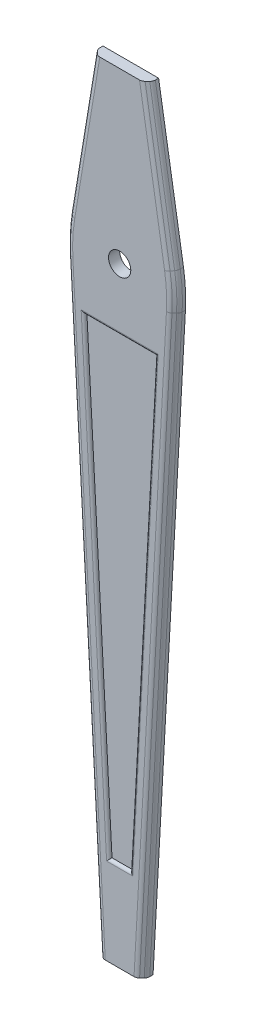
SolidWorks part; units mm, degrees
ref_plane "Front" through (0, 0, 0) normal (0, 0, 1) x (1, 0, 0)
ref_plane "Top" through (0, 0, 0) normal (0, 1, 0) x (1, 0, 0)
ref_plane "Right" through (0, 0, 0) normal (1, 0, 0) x (0, 0, -1)
sketch "Эскиз1" plane through (0, 0, 0) normal (0, 0, 1) x (1, 0, 0)
  line L0 (-1.8457, 0) -> (2.0484, 0) construction
  line L1 (0, 3.2545) -> (0, -2.3671) construction
  line L2 (-0.9468, 0.3235) -> (-0.5, 3.04)
  line L3 (-0.5, 3.04) -> (0.5, 3.04)
  line L4 (-0.9821, -0.3274) -> (-0.4, -10.96)
  line L5 (-0.4, -10.96) -> (0.4, -10.96)
  line L6 (0.9821, -0.3274) -> (0.4, -10.96)
  line L7 (0.9468, 0.3235) -> (0.5, 3.04)
  circle A0 centre (0, 0) radius 0.2
  arc A1 (0.9821, -0.3274) -> (0.9468, 0.3235) centre (-2.0134, -0.1634) ccw
  arc A2 (-0.9468, 0.3235) -> (-0.9821, -0.3274) centre (2.0134, -0.1634) ccw
  point P13 (0, -10.96)
  point P15 (0, 3.04)
  point P17 (1, 0)
  point P20 (-1, 0)
  dimension "D1" = 0.4
  dimension "D7" = 3
  dimension "D2" = 10.96
  dimension "D3" = 0.4
  dimension "D4" = 0.5
  dimension "D5" = 1
  dimension "D6" = 3.04
extrude "Бобышка-Вытянуть1" add sketch "Эскиз1" along normal blind 0.2
chamfer "Фаска1" distance 0.1 angle 45 6 edges at (0.691, -5.6437, 0.2) (0.7234, 1.6818, 0.2) (-0.7234, 1.6818, 0.2) (-0.691, -5.6437, 0.2) (0.9822, -0.001, 0.2) (-0.9822, -0.001, 0.2)
sketch "Эскиз2" plane through (0, 0, 0.2) normal (0, 0, 1) x (1, 0, 0)
  line L2 (-0.6825, -0.311) -> (-0.1001, -10.9491)
  line L3 (-0.6389, -1.1086) -> (-0.1872, -9.3583)
  line L5 (0.1001, -10.9491) -> (0.6825, -0.311)
  line L6 (0.1872, -9.3583) -> (0.6389, -1.1086)
  line L10 (-0.1872, -9.3583) -> (0.1872, -9.3583)
  line L11 (-0.2999, -10.96) -> (0.2999, -10.96) construction
  line L12 (-0.6389, -1.1086) -> (0.6389, -1.1086)
  dimension "D1" = 0.2
  dimension "D2" = 0.2
extrude "Вырез-Вытянуть1" cut sketch "Эскиз2" against normal blind 0.05
fillet "Скругление1" radius 0.1 12 edges at (0.7234, 1.6818, 0.1) (0.9822, -0.001, 0.1) (-0.7234, 1.6818, 0.1) (-0.9822, -0.001, 0.1) (0.6234, 1.6736, 0.2) (0.8823, -0.0064, 0.2) (-0.591, -5.6409, 0.2) (-0.8823, -0.0064, 0.2) (0.691, -5.6437, 0.1) (-0.691, -5.6437, 0.1) (0.591, -5.6409, 0.2) (-0.6234, 1.6736, 0.2)
fillet "Скругление2" radius 0.05 4 edges at (0, -9.3583, 0.2) (-0.413, -5.2335, 0.2) (0.413, -5.2335, 0.2) (0, -1.1086, 0.2)
